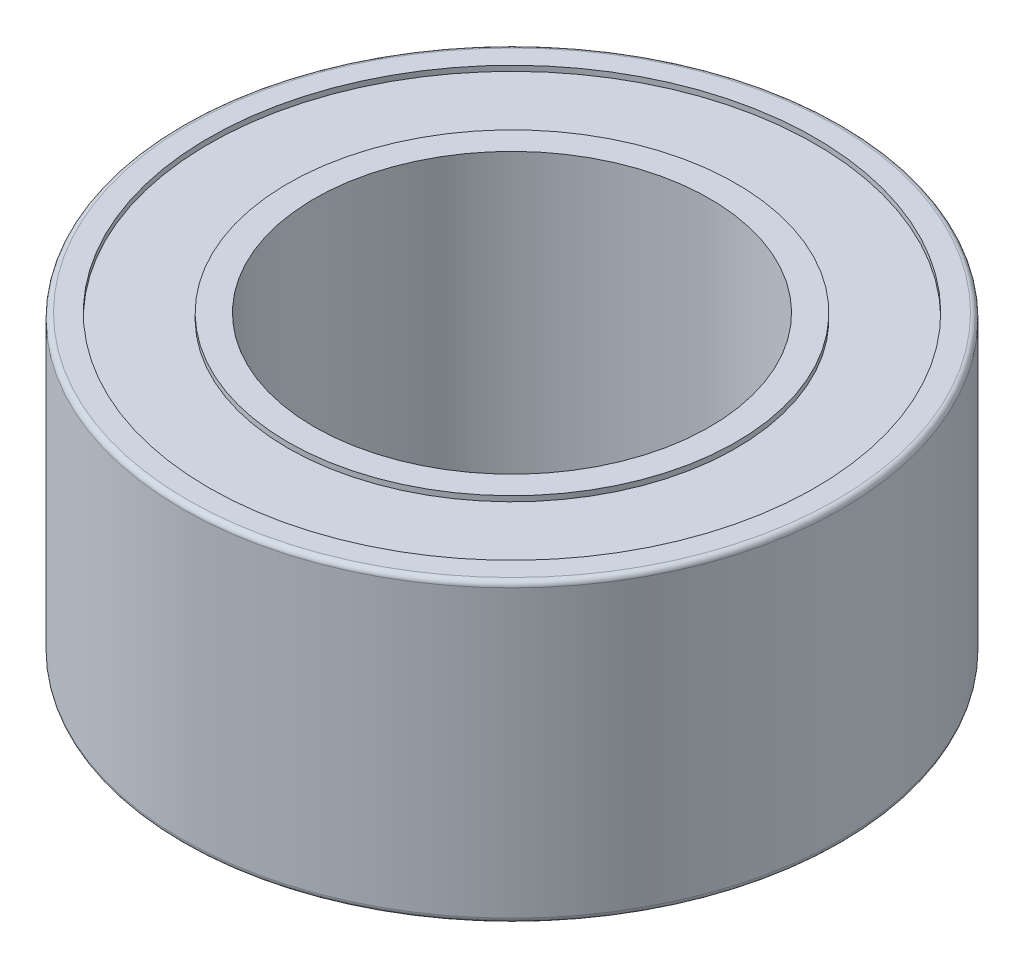
SolidWorks part; units mm, degrees
ref_plane "Front Plane" through (0, 0, 0) normal (0, 0, 1) x (1, 0, 0)
ref_plane "Top Plane" through (0, 0, 0) normal (0, 1, 0) x (1, 0, 0)
ref_plane "Right Plane" through (0, 0, 0) normal (1, 0, 0) x (0, 0, -1)
sketch "Sketch1" plane through (0, 0, 0) normal (0, 1, 0) x (1, 0, 0)
  circle A0 centre (0, 0) radius 7.9375
  circle A1 centre (0, 0) radius 4.7625
  dimension "D1" = 9.525
  dimension "D2" = 15.875
extrude "Boss-Extrude1" add sketch "Sketch1" along normal blind 7.1437
sketch "Sketch2" plane through (0, 7.1437, 0) normal (0, 1, 0) x (1, 0, 0)
  circle A0 centre (0, 0) radius 5.3975
  circle A1 centre (0, 0) radius 7.3025
  dimension "D1" = 10.795
  dimension "D2" = 14.605
extrude "Cut-Extrude1" cut sketch "Sketch2" against normal blind 0.127
sketch "Sketch3" plane through (0, 0, 0) normal (0, -1, 0) x (1, 0, 0)
  circle A0 centre (0, 0) radius 5.3975 construction
  circle A1 centre (0, 0) radius 7.3025 construction
  circle A2 centre (0, 0) radius 5.3975
  circle A3 centre (0, 0) radius 7.3025
extrude "Cut-Extrude3" cut sketch "Sketch3" against normal blind 0.127
fillet "Fillet1" radius 0.127 2 edges at (0, 0, 7.9375) (0, 7.1437, 7.9375)
